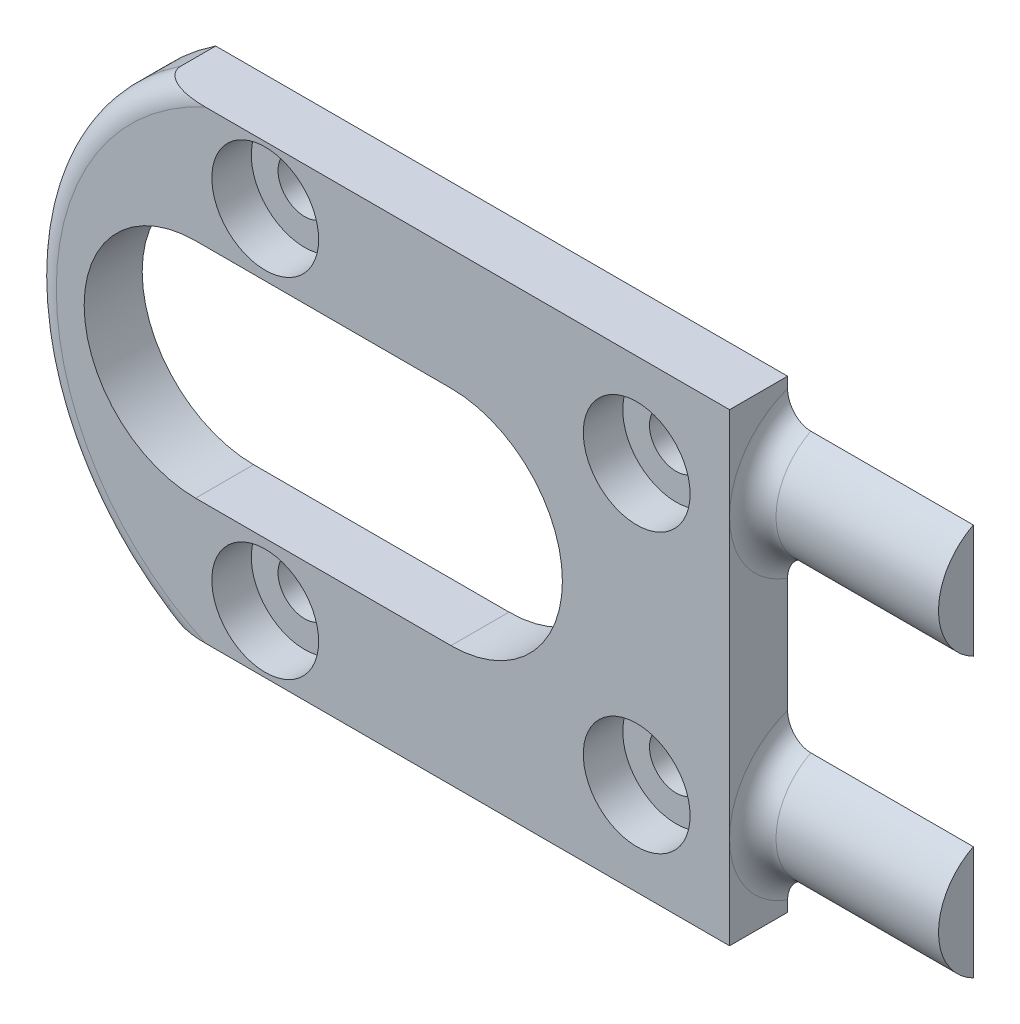
SolidWorks part; units mm, degrees
material "ABS"
ref_plane "Front Plane" through (0, 0, 0) normal (0, 0, 1) x (1, 0, 0)
ref_plane "Top Plane" through (0, 0, 0) normal (0, 1, 0) x (1, 0, 0)
ref_plane "Right Plane" through (0, 0, 0) normal (1, 0, 0) x (0, 0, -1)
sketch "Sketch1" plane through (0, 0, 0) normal (0, 0, 1) x (1, 0, 0)
  line L1 (15, -10) -> (-9.6332, -10)
  line L2 (15, -10) -> (15, 10)
  line L3 (15, 10) -> (-9.6332, 10)
  line L5 (15, -10) -> (-11.9651, 7.9767) construction
  line L6 (15, 10) -> (-11.9651, -7.9767) construction
  arc A0 (-9.6332, -10) -> (-9.6332, 10) centre (-3, 0) cw
  point P0 (0, 0)
  dimension "D3" = 12
  dimension "D4" = 15
  dimension "D1" = 3
  dimension "D2" = 20
extrude "Boss-Extrude1" add sketch "Sketch1" along normal blind 2.5
sketch "Sketch2" plane through (15, 0, 0) normal (1, 0, 0) x (0, 0, -1)
  line L0 (0, -10) -> (0, 10) construction
  line L1 (-2.5, 10) -> (0, 10) construction
  line L2 (-2.5, -10) -> (0, -10) construction
  line L3 (0, -8.4495) -> (0, -3.5505)
  line L4 (0, 3.5505) -> (0, 8.4495)
  arc A0 (0, 8.4495) -> (0, 3.5505) centre (1.25, 6) ccw
  arc A1 (0, -3.5505) -> (0, -8.4495) centre (1.25, -6) ccw
  dimension "D1" = 5.5
  dimension "D4" = 5.5
  dimension "D2" = 1.25
  dimension "D3" = 4
  dimension "D5" = 4
  dimension "D6" = 1.25
extrude "Boss-Extrude2" add sketch "Sketch2" along normal blind 8
fillet "Fillet2" radius 1 2 edges at (15, 6, 1.5) (15, -6, 1.5)
sketch "Sketch3" plane through (0, 0, 0) normal (0, 0, -1) x (-1, 0, 0)
  line L0 (8, 0) -> (-3, 0) construction
  line L1 (8, -4.8) -> (-3, -4.8)
  line L2 (8, 4.8) -> (-3, 4.8)
  arc A0 (8, -4.8) -> (8, 4.8) centre (8, 0) ccw
  arc A1 (-3, 4.8) -> (-3, -4.8) centre (-3, 0) ccw
  point P1 (2.5, 0)
  dimension "D1" = 4.8
  dimension "D2" = 8
  dimension "D3" = 3
extrude "Cut-Extrude1" cut sketch "Sketch3" against normal blind 8
sketch "Sketch4" plane through (0, 0, 2.5) normal (0, 0, 1) x (1, 0, 0)
  line L0 (-9.6332, -10) -> (15, -10) construction
  line L1 (15, 10) -> (-9.6332, 10) construction
  circle A0 centre (-5, 7.5) radius 2.3
  circle A1 centre (11, 6) radius 2.3
  circle A2 centre (11, -6) radius 2.3
  circle A3 centre (-5, -7.5) radius 2.3
  dimension "D1" = 4.6
  dimension "D2" = 2.5
  dimension "D3" = 2.5
  dimension "D4" = 5
  dimension "D5" = 4
  dimension "D6" = 4
  dimension "D7" = 16
extrude "Cut-Extrude2" cut sketch "Sketch4" against normal blind 1.7
sketch "Sketch5" plane through (0, 0, 0.8) normal (0, 0, 1) x (1, 0, 0)
  circle A0 centre (-5, 7.5) radius 1.15
  circle A1 centre (11, 6) radius 1.15
  circle A2 centre (11, -6) radius 1.15
  circle A3 centre (-5, -7.5) radius 1.15
  dimension "D1" = 2.3
extrude "Cut-Extrude3" cut sketch "Sketch5" against normal through all
fillet "Fillet3" radius 1 1 edges at (-15, 0, 2.5)
